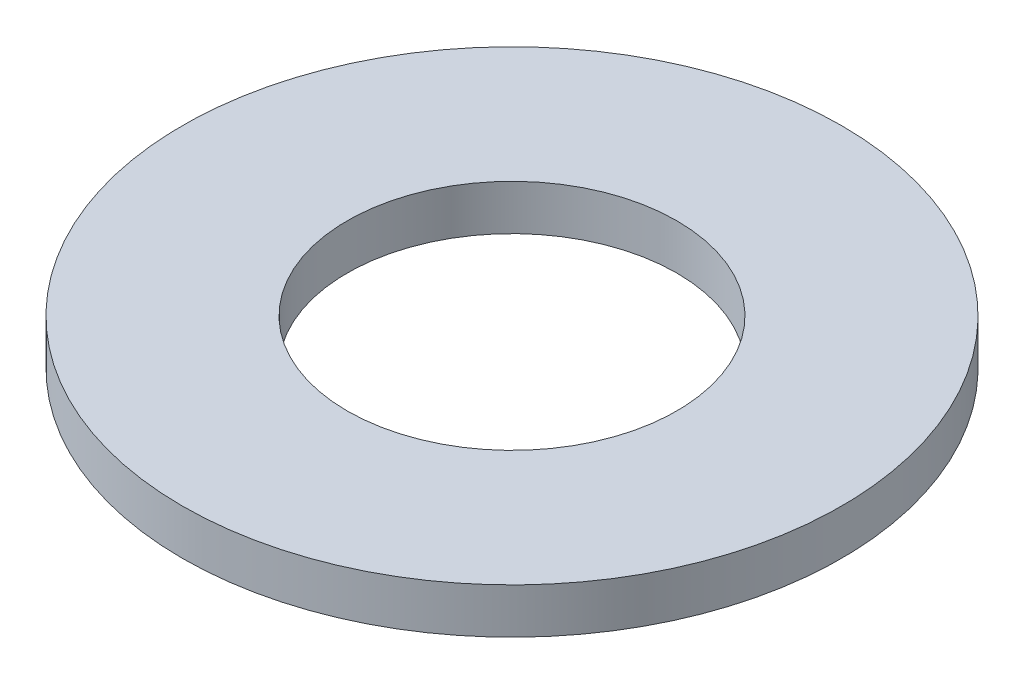
SolidWorks part; units mm, degrees
ref_plane "Front Plane" through (0, 0, 0) normal (0, 0, 1) x (1, 0, 0)
ref_plane "Top Plane" through (0, 0, 0) normal (0, 1, 0) x (1, 0, 0)
ref_plane "Right Plane" through (0, 0, 0) normal (1, 0, 0) x (0, 0, -1)
sketch "Sketch1" plane through (0, 0, 0) normal (0, 1, 0) x (1, 0, 0)
  circle A0 centre (0, 0) radius 80
  dimension "FLANGE_OD" = 160
extrude "Boss-Extrude1" add sketch "Sketch1" along normal blind 11
sketch "Sketch2" plane through (0, 0, 0) normal (0, 1, 0) x (1, 0, 0)
  circle A0 centre (0, 0) radius 40
  dimension "BORE_D" = 80
extrude "Cut-Extrude1" cut sketch "Sketch2" along normal through all
sketch "Sketch3" plane through (0, 11, 0) normal (0, 1, 0) x (1, 0, 0)
  circle A0 centre (0, 0) radius 36.5341 construction
  circle A1 centre (-36.5341, 0) radius 2.2271
  dimension "BOLT_D" = 4.4542
  dimension "BOLT_PCD" = 73.0682
extrude "Cut-Extrude2" cut sketch "Sketch3" against normal blind 9.1668 rebuild error yes
pattern_circular "CirPattern1" count 8 over 360 rebuild error yes
